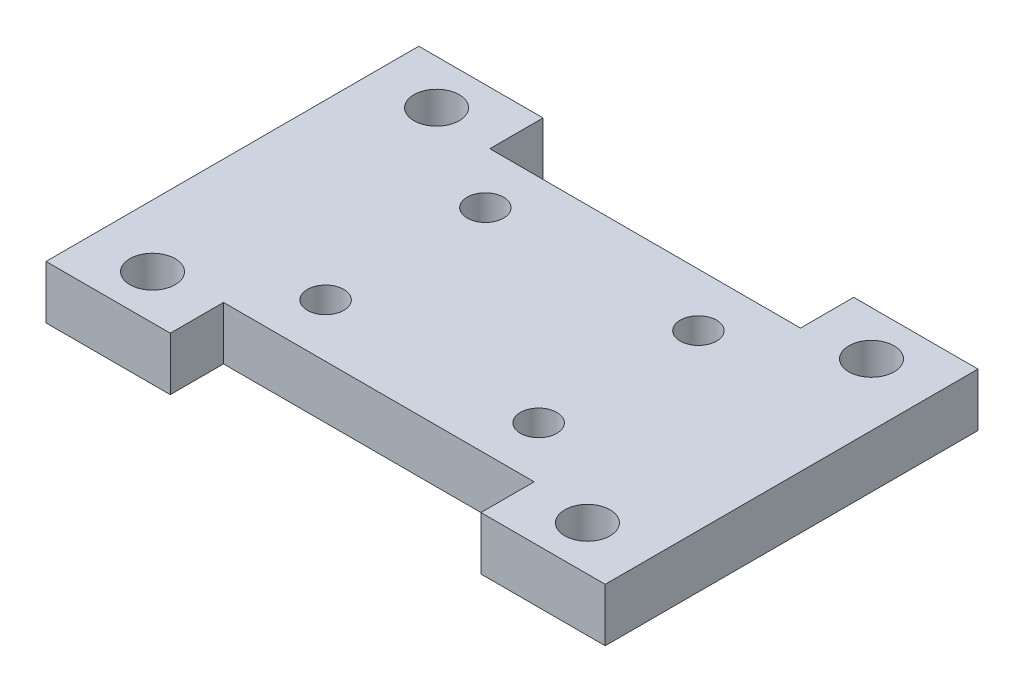
SolidWorks part; units mm, degrees
material "Alloy Steel"
ref_plane "Front Plane" through (0, 0, 0) normal (0, 0, 1) x (1, 0, 0)
ref_plane "Top Plane" through (0, 0, 0) normal (0, 1, 0) x (1, 0, 0)
ref_plane "Right Plane" through (0, 0, 0) normal (1, 0, 0) x (0, 0, -1)
sketch "Sketch1" plane through (0, 0, 0) normal (0, 1, 0) x (1, 0, 0)
  line L0 (0, 15) -> (0, -15) construction
  line L1 (-17.5, -15) -> (17.5, -15)
  line L3 (-17.5, 15) -> (17.5, 15)
  line L5 (-17.5, -15) -> (17.5, 15) construction
  line L6 (-17.5, 15) -> (17.5, -15) construction
  line L7 (-24.4406, 0) -> (25.4895, 0) construction
  line L8 (17.5, 15) -> (17.5, 21)
  line L9 (17.5, 21) -> (31.5, 21)
  line L10 (31.5, 21) -> (31.5, -21)
  line L11 (31.5, -21) -> (17.5, -21)
  line L12 (17.5, -21) -> (17.5, -15)
  line L13 (-17.5, -21) -> (-17.5, -15)
  line L14 (-31.5, -21) -> (-17.5, -21)
  line L15 (-31.5, 21) -> (-31.5, -21)
  line L16 (-17.5, 21) -> (-31.5, 21)
  line L17 (-17.5, 15) -> (-17.5, 21)
  circle A0 centre (-12, 9) radius 2.05
  circle A1 centre (12, 9) radius 2.05
  circle A2 centre (12, -9) radius 2.05
  circle A3 centre (-12, -9) radius 2.05
  circle A4 centre (24.5, 16) radius 2.55
  circle A5 centre (24.5, -16) radius 2.55
  circle A6 centre (-24.5, -16) radius 2.55
  circle A7 centre (-24.5, 16) radius 2.55
  point P0 (0, 0)
  point P20 (31.5, 0)
  point P22 (0, 0)
  point P25 (24.5, 21)
  dimension "D3" = 4.1
  dimension "D11" = 5.1
  dimension "D1" = 35
  dimension "D2" = 30
  dimension "D4" = 12
  dimension "D5" = 9
  dimension "D6" = 14
  dimension "D7" = 42
  dimension "D8" = 14
  dimension "D9" = 35
  dimension "D10" = 16
extrude "Boss-Extrude1" add sketch "Sketch1" along normal blind 6
